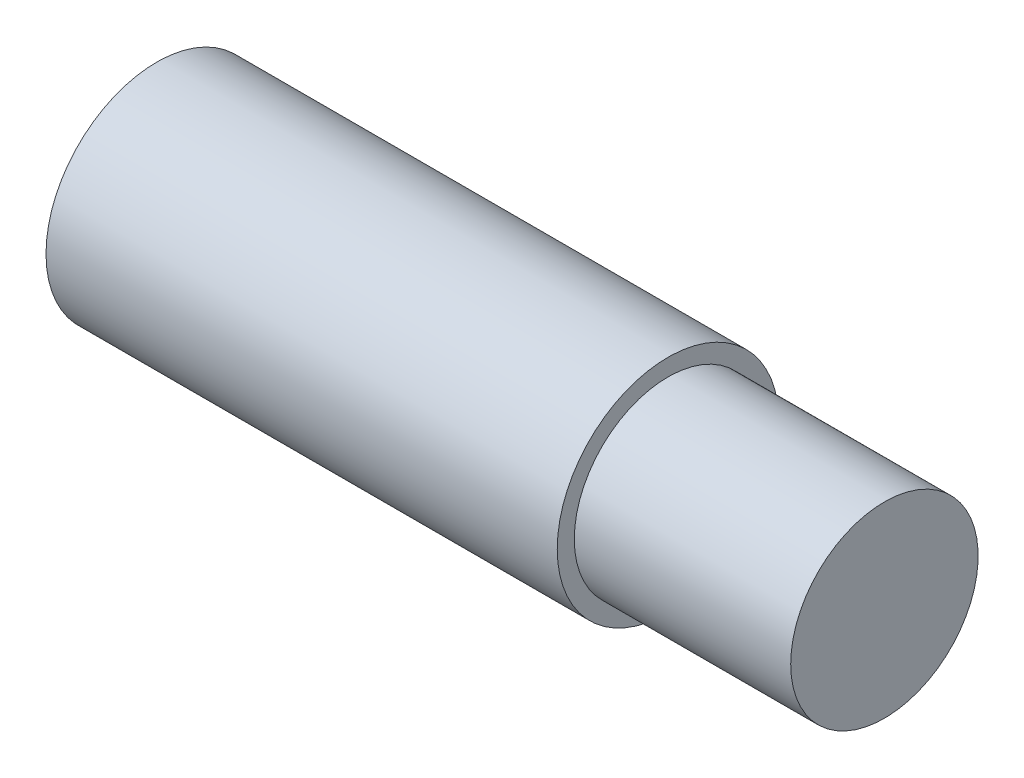
SolidWorks part; units mm, degrees
ref_plane "Front Plane" through (0, 0, 0) normal (0, 0, 1) x (1, 0, 0)
ref_plane "Top Plane" through (0, 0, 0) normal (0, 1, 0) x (1, 0, 0)
ref_plane "Right Plane" through (0, 0, 0) normal (1, 0, 0) x (0, 0, -1)
sketch "Fill_Nipple Sketch" plane through (0, 0, 0) normal (0, 0, 1) x (1, 0, 0)
  line L0 (-1000, 0) -> (1000, 0) construction
  line L1 (12.7, 0) -> (12.7, 5.5)
  line L2 (12.7, 5.5) -> (0, 5.5)
  line L3 (0, 5.5) -> (0, 6.5)
  line L4 (0, 6.5) -> (-30, 6.5)
  line L5 (-30, 6.5) -> (-30, 0)
  line L6 (-30, 0) -> (12.7, 0)
revolve "Fill_Nipple" add sketch "Fill_Nipple Sketch" angle 360 about L0
ref_axis "Engine Axis" through (14.835, 0, 0) along (-1, 0, 0)
